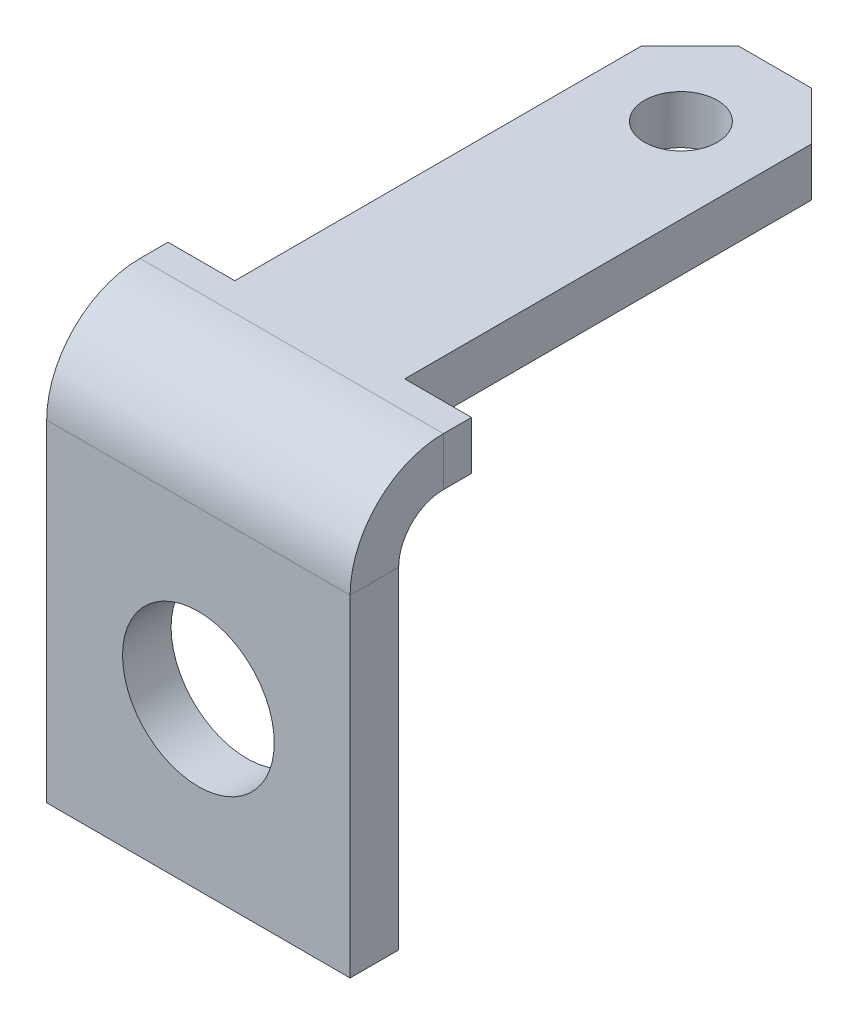
SolidWorks part; units mm, degrees
note: The reader was unsure of these and kept them because the rebuilt part matched: flange length of "边线-法兰1".
ref_plane "前视基准面" through (0, 0, 0) normal (0, 0, 1) x (1, 0, 0)
ref_plane "上视基准面" through (0, 0, 0) normal (0, 1, 0) x (1, 0, 0)
ref_plane "右视基准面" through (0, 0, 0) normal (1, 0, 0) x (0, 0, -1)
sketch "草图1" plane through (0, 0, 0) normal (0, 0, 1) x (1, 0, 0)
  line L0 (0, -9.6598) -> (0, 15.7475) construction
  line L1 (-2.5, 3.5) -> (2.5, 3.5)
  line L2 (-2.5, 3.5) -> (-2.5, -3.5)
  line L3 (-2.5, -3.5) -> (2.5, -3.5)
  line L4 (2.5, 3.5) -> (2.5, -3.5)
  line L5 (-7.2033, 0) -> (10.3863, 0) construction
  dimension "D1" = 7
  dimension "D2" = 5
sheet metal parameters "钣金1" thickness 0.8 parameters "D1"=0.7366
base flange "基体-法兰1" sketch "草图1" thickness 0.8 reverse thickness direction no parameters "D1"=0.7366
edge flange "边线-法兰1" sketch "草图6" flange angle 90 flange length 9.5 flange position material inside bend radius 0.7366 thickness 0.8 relief rectangular parameters "D6"=10
sketch "草图6" plane through (0, 3.5, -0.8) normal (0, 1, 0) x (1, 0, 0)
  line L0 (2.5, 0) -> (-2.5, 0) construction
  line L1 (2.5, 0) -> (-2.5, 0)
  line L2 (-2.5, 0) -> (-2.5, 8.7)
  line L3 (-2.5, 8.7) -> (2.5, 8.7)
  line L4 (2.5, 8.7) -> (2.5, 0)
bend "边线折弯1" bend radius 0.7366 bend angle 90 parameters "D5"=1
sketch "草图7" plane through (0, 0, -0.8) normal (0, 0, -1) x (-1, 0, 0)
  line L0 (-4.184, -0.7683) -> (5.451, -0.7683) construction
  line L1 (-2.5, 1.9634) -> (2.5, 1.9634) construction
  line L2 (2.5, -3.5) -> (-2.5, -3.5) construction
  line L3 (0, 1.5519) -> (0, -4.6811) construction
  circle A0 centre (0, -0.7683) radius 1.25
  dimension "D1" = 2.5
extrude "切除-拉伸1" cut sketch "草图7" against normal blind 10 normal cut yes
sketch "草图8" plane through (0, 3.5, 0) normal (0, 1, 0) x (1, 0, 0)
  line L0 (0, -1.6347) -> (0, 10.6777) construction
  line L2 (1.4, 9.5) -> (1.4, 2)
  line L3 (-2.5, 9.5) -> (-1.4, 9.5)
  line L4 (-2.5, 9.5) -> (-2.5, 2)
  line L5 (-2.5, 2) -> (-1.4, 2)
  line L6 (-1.4, 9.5) -> (-1.4, 2)
  line L7 (2.5, 2) -> (1.4, 2)
  line L8 (2.5, 9.5) -> (2.5, 2)
  line L9 (2.5, 9.5) -> (1.4, 9.5)
  dimension "D1" = 7.5
  dimension "D2" = 2.8
extrude "切除-拉伸2" cut sketch "草图8" against normal blind 10 normal cut yes
sketch "草图9" plane through (0, 3.5, 0) normal (0, 1, 0) x (1, 0, 0)
  line L0 (0, -2.4042) -> (0, 11.8617) construction
  circle A0 centre (0, 7.9513) radius 0.6
  dimension "D1" = 1.2
extrude "切除-拉伸3" cut sketch "草图9" against normal blind 10 normal cut yes
chamfer "倒角1" distance 0.8 angle 45 2 edges at (1.4, 3.1, -9.5) (-1.4, 3.1, -9.5)
flat pattern "平板型式1" [suppressed]
sketch "折弯-线1" plane through (0, 0, 0) normal (0, 1, 0) x (1, 0, 0)
sketch3d "边界框1" [suppressed]
  line L0 (-2.5, 3.5, 0) -> (-2.5, -3.5, 0) construction
  line L1 (2.5, 3.5, 0) -> (2.5, -3.5, 0) construction
  line L2 (-2.5, 3.5, 0) -> (2.5, 3.5, 0) construction
  line L3 (-2.5, -3.5, 0) -> (2.5, -3.5, 0) construction
bend of the flat pattern "展开-<边线折弯1>1"
